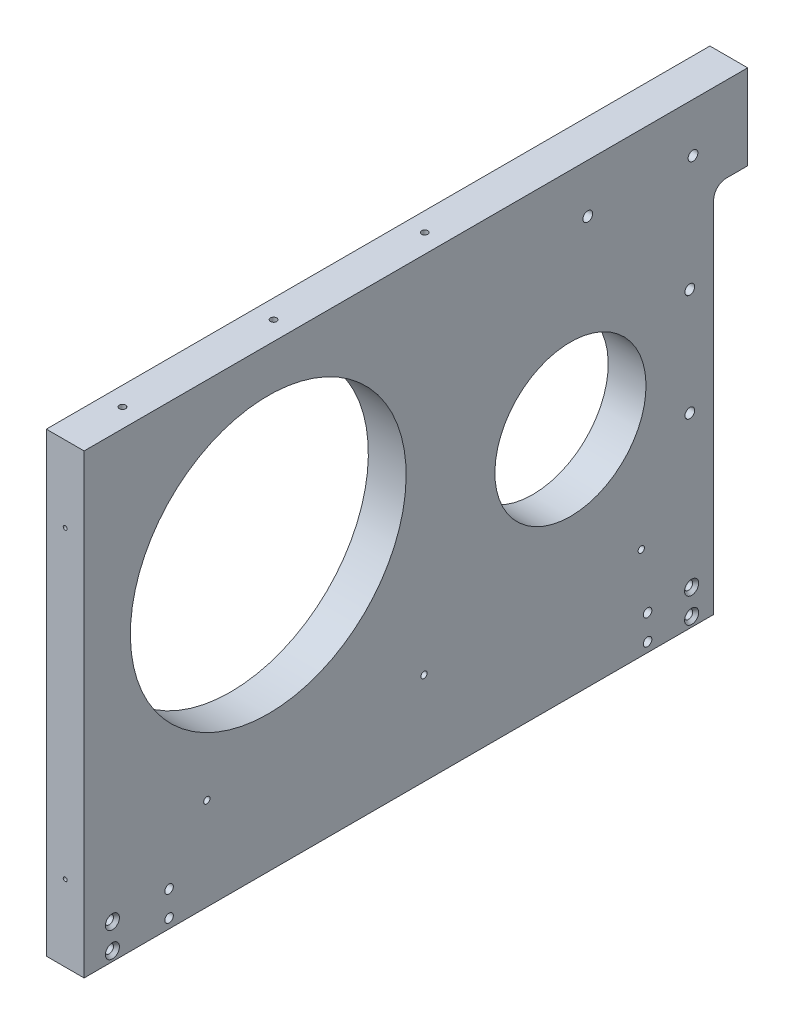
SolidWorks part; units mm, degrees
material "MDF"
ref_plane "Front Plane" through (0, 0, 0) normal (0, 0, 1) x (1, 0, 0)
ref_plane "Top Plane" through (0, 0, 0) normal (0, 1, 0) x (1, 0, 0)
ref_plane "Right Plane" through (0, 0, 0) normal (1, 0, 0) x (0, 0, -1)
sketch "Sketch1" plane through (0, 0, 0) normal (0, 0, 1) x (1, 0, 0)
  line L0 (-296.7037, -233.3625) -> (-271.672, -233.3625) construction
  line L1 (-290.722, -3.175) -> (-271.672, -3.175)
  line L2 (-290.722, -3.175) -> (-290.722, -233.3625)
  line L3 (-290.722, -233.3625) -> (-271.672, -233.3625)
  line L4 (-271.672, -3.175) -> (-271.672, -233.3625)
  dimension "D1" = 19.05
extrude "Boss-Extrude1" add sketch "Sketch1" along normal blind 342.9
sketch "Sketch2" plane through (0, 0, 0) normal (0, 0, 1) x (1, 0, 0)
  line L1 (-199.4987, -156.8808) -> (-434.4987, -156.8808) construction
  line L2 (-271.672, -3.175) -> (-290.722, -3.175) construction
  line L3 (-271.672, -156.8808) -> (-290.722, -156.8808) construction
  line L4 (-271.672, -160.0558) -> (-290.722, -160.0558)
  line L5 (-290.722, -3.175) -> (-271.672, -3.175)
  line L6 (-271.672, -160.0558) -> (-271.672, -3.175)
  line L9 (-290.722, -3.175) -> (-290.722, -160.0558)
  line L10 (-271.672, -233.3625) -> (-271.672, -3.175) construction
  line L11 (-290.722, -3.175) -> (-290.722, -233.3625) construction
  line L12 (-199.4987, -160.0558) -> (-434.4987, -160.0558) construction
  line L13 (-199.4987, -156.8808) -> (-434.4987, -156.8808) construction
  dimension "D1" = 3.175
extrude "Cut-Extrude1" cut sketch "Sketch2" along normal blind 8.255
hole_wizard "15/64 (0.23438) Diameter Hole3" positions "Sketch7" profile "Sketch8" hole size "15/64" standard "ANSI Inch"
sketch "Sketch7" plane through (-182.4037, 1936.854, -6.35) normal (0, 0, -1) x (1, 0, 0)
  point P0 (-262.8265, 2051.0885)
  point P3 (-262.8265, 2014.0687)
  point P6 (-262.8265, 1977.0488)
  point P9 (-98.7933, 2115.9598)
  point P12 (-98.7933, 2151.1665)
sketch "Sketch8" plane through (-445.2302, -114.2346, -6.35) normal (1, 0, 0) x (0, 1, 0)
  line L0 (0, 0) -> (0, 14.4885)
  line L1 (0, 14.4885) -> (2.9766, 12.7)
  line L2 (2.9766, 12.7) -> (2.9766, 0)
  line L3 (2.9766, 0) -> (0, 0)
  line L4 (0, 14.4885) -> (-2.9766, 12.7) construction
  line L5 (0, -6.35) -> (0, 107.95) construction
  dimension "Hole Dia." = 5.9533
  dimension "Hole Depth" = 12.7
  dimension "Drill Angle" = 118
hole_wizard "5/64 (0.07813) Diameter Hole1" positions "Sketch9" profile "Sketch10" hole size "5/64" standard "ANSI Inch"
sketch "Sketch9" plane through (-182.4037, 15.875, 6471.4599) normal (0, 1, 0) x (1, 0, 0)
  line L1 (-1.27, 6109.5099) -> (-1.27, 6338.7449) construction
  point P0 (-262.8265, 6157.4524)
  point P6 (-98.7933, 6157.4524)
  point P18 (-262.8265, 6233.6524)
  point P19 (-98.7933, 6233.6524)
  point P22 (-262.8265, 6309.8524)
  point P23 (-98.7933, 6309.8524)
  point P24 (-267.97, 6119.0349)
  point P34 (-115.57, 6119.0349)
  point P37 (-1.27, 6119.0349)
  point P40 (113.03, 6119.0349)
  point P44 (265.43, 6119.0349)
  point P55 (98.7933, 6309.8524)
  point P56 (262.8265, 6309.8524)
  point P59 (98.7933, 6233.6524)
  point P60 (262.8265, 6233.6524)
  point P63 (98.7933, 6157.4524)
  point P64 (262.8265, 6157.4524)
sketch "Sketch10" plane through (-445.2302, 15.875, 314.0075) normal (1, 0, 0) x (0, 0, 1)
  line L0 (0, 0) -> (0, 39.0539)
  line L1 (0, 39.0539) -> (1.5875, 38.1)
  line L2 (1.5875, 38.1) -> (1.5875, 4.0177)
  line L3 (1.5875, 4.0177) -> (5.08, 0)
  line L4 (5.08, 0) -> (0, 0)
  line L5 (-1.5875, 4.0177) -> (-5.08, 0) construction
  line L6 (0, 39.0539) -> (-1.5875, 38.1) construction
  line L7 (0, -6.35) -> (0, 107.95) construction
  dimension "Hole Dia." = 3.175
  dimension "Hole Depth" = 38.1
  dimension "Near C'Sink Dia." = 10.16
  dimension "Near C'Sink Angle" = 82
  dimension "Drill Angle" = 118
hole_wizard "5/64 (0.07813) Diameter Hole2" positions "Sketch11" profile "Sketch12" hole size "5/64" standard "ANSI Inch"
sketch "Sketch11" plane through (-182.4037, 1936.854, 361.95) normal (0, 0, 1) x (-1, 0, 0)
  line L23 (262.8265, 2088.1084) -> (262.8265, 2038.7486)
  line L24 (262.8265, 2038.7486) -> (262.8265, 1989.3888)
  line L25 (262.8265, 1989.3888) -> (262.8265, 2038.7486)
  line L26 (262.8265, 2038.7486) -> (262.8265, 1989.3888)
  line L27 (262.8265, 1989.3888) -> (262.8265, 1940.029)
  line L33 (98.7933, 2170.2165) -> (98.7933, 2131.8519)
  line L35 (98.7933, 2131.8519) -> (98.7933, 2093.4873)
  line L36 (98.7933, 2093.4873) -> (98.7933, 2055.1227)
  line L37 (98.7933, 2055.1227) -> (98.7933, 2016.7581)
  line L38 (98.7933, 2016.7581) -> (98.7933, 1978.3935)
  line L39 (98.7933, 1978.3935) -> (98.7933, 1940.029)
  line L44 (89.2683, 2123.544) -> (53.561, 2123.544)
  line L46 (53.561, 2123.544) -> (17.8537, 2123.544)
  line L47 (17.8537, 2123.544) -> (-17.8537, 2123.544)
  line L48 (-17.8537, 2123.544) -> (-53.561, 2123.544)
  line L49 (-53.561, 2123.544) -> (-89.2683, 2123.544)
  line L53 (0, 2170.2165) -> (-0.3175, 1940.029) construction
  line L55 (-99.3221, 1978.6668) -> (-99.4279, 1940.3024)
  line L56 (-99.2163, 2017.0312) -> (-99.3221, 1978.6668)
  line L57 (-99.1104, 2055.3957) -> (-99.2163, 2017.0312)
  line L58 (-99.0046, 2093.7601) -> (-99.1104, 2055.3957)
  line L59 (-98.8988, 2132.1245) -> (-99.0046, 2093.7601)
  line L60 (-98.7929, 2170.489) -> (-98.8988, 2132.1245)
  line L61 (-263.3243, 1990.1145) -> (-263.4605, 1940.7549)
  line L62 (-263.1882, 2039.4741) -> (-263.3243, 1990.1145)
  line L63 (-263.3243, 1990.1145) -> (-263.1882, 2039.4741)
  line L64 (-263.1882, 2039.4741) -> (-263.3243, 1990.1145)
  line L65 (-263.052, 2088.8338) -> (-263.1882, 2039.4741)
  point P71 (262.8265, 1964.7089)
  point P79 (262.8265, 2063.4285)
  point P95 (98.7933, 2131.8519)
  point P103 (98.7933, 1978.3935)
  point P126 (53.561, 2123.544)
  point P134 (-53.561, 2123.544)
  point P162 (-98.7933, 1978.3935)
  point P166 (-98.7933, 2131.8519)
  point P167 (-262.8265, 2063.4285)
  point P169 (-262.8265, 1964.7089)
sketch "Sketch12" plane through (80.4228, -27.8549, 361.95) normal (1, 0, 0) x (0, -1, 0)
  line L0 (0, 0) -> (0, 38.6962)
  line L1 (0, 38.6962) -> (0.9923, 38.1)
  line L2 (0.9923, 38.1) -> (0.9923, 4.7024)
  line L3 (0.9923, 4.7024) -> (5.08, 0)
  line L4 (5.08, 0) -> (0, 0)
  line L5 (-0.9923, 4.7024) -> (-5.08, 0) construction
  line L6 (0, 38.6962) -> (-0.9923, 38.1) construction
  line L7 (0, -6.35) -> (0, 107.95) construction
  dimension "Hole Dia." = 1.9845
  dimension "Hole Depth" = 38.1
  dimension "Near C'Sink Dia." = 10.16
  dimension "Near C'Sink Angle" = 82
  dimension "Drill Angle" = 118
hole_wizard "1/8 (0.125) Diameter Hole1" positions "Sketch13" profile "Sketch14" hole size "1/8" standard "ANSI Inch" end condition up to next
sketch "Sketch13" plane through (-290.722, 0, 0) normal (-1, 0, 0) x (0, 0, 1)
  line L4 (317.5, -186.69) -> (280.9875, -186.69)
  line L5 (317.5, -193.04) -> (317.5, -180.34) construction
  line L6 (280.9875, -186.69) -> (244.475, -186.69)
  line L7 (244.475, -186.69) -> (207.9625, -186.69)
  line L8 (207.9625, -186.69) -> (171.45, -186.69)
  line L9 (171.45, -186.69) -> (134.9375, -186.69)
  line L10 (134.9375, -186.69) -> (98.425, -186.69)
  line L11 (98.425, -186.69) -> (61.9125, -186.69)
  line L12 (61.9125, -186.69) -> (25.4, -186.69)
  point P10 (280.9875, -186.69)
  point P18 (171.45, -186.69)
  point P24 (61.9125, -186.69)
sketch "Sketch14" plane through (-290.722, -186.69, 61.9125) normal (0, 1, 0) x (0, 0, 1)
  line L0 (0, 0) -> (0, 19.05)
  line L1 (0, 19.05) -> (1.5875, 19.05)
  line L2 (1.5875, 19.05) -> (1.5875, 3.4925)
  line L3 (1.5875, 3.4925) -> (5.08, 0)
  line L5 (5.08, 0) -> (0, 0)
  line L6 (-1.5875, 3.4925) -> (-5.08, 0) construction
  line L11 (0, -6.35) -> (0, 107.95) construction
  dimension "Thru Hole Dia." = 3.175
  dimension "Thru Hole Depth" = 19.05
  dimension "Near C'Sink Dia." = 10.16
  dimension "Near C'Sink Angle" = 90
hole_wizard "#8 Clearance Hole1" positions "Sketch15" profile "Sketch16" hole size "#8" standard "ANSI Inch" end condition up to next
sketch "Sketch15" plane through (-271.672, 0, 0) normal (1, 0, 0) x (0, 0, -1)
  point P0 (-88.9, -27.7495)
  point P2 (-35.8275, -27.7495)
sketch "Sketch16" plane through (-271.672, -27.7495, 88.9) normal (0, 1, 0) x (0, 0, -1)
  line L0 (0, 0) -> (0, 19.05)
  line L1 (0, 19.05) -> (2.4574, 19.05)
  line L2 (2.4574, 19.05) -> (2.4574, 0)
  line L5 (2.4574, 0) -> (0, 0)
  line L11 (0, -6.35) -> (0, 107.95) construction
  dimension "Thru Hole Dia." = 4.9149
  dimension "Thru Hole Depth" = 19.05
hole_wizard "CSK for #6 Flat Head Machine Screw (100)1" positions "Sketch18" profile "Sketch19" countersink size "#6" standard "ANSI Inch" end condition up to next
sketch "Sketch18" plane through (-271.672, 0, 0) normal (1, 0, 0) x (0, 0, -1)
  point P0 (-36.5125, -215.9)
  point P3 (-36.5125, -228.6)
  point P6 (-328.6125, -215.9)
  point P9 (-328.6125, -228.6)
sketch "Sketch19" plane through (-271.672, -215.9, 36.5125) normal (0, 1, 0) x (0, 0, -1)
  line L0 (0, 0) -> (0, 19.05)
  line L1 (0, 19.05) -> (2.1526, 19.05)
  line L2 (2.1526, 19.05) -> (2.1526, 1.5998)
  line L3 (2.1526, 1.5998) -> (3.5433, 0)
  line L5 (3.5433, 0) -> (0, 0)
  line L6 (-2.1526, 1.5998) -> (-3.5433, 0) construction
  line L11 (0, -6.35) -> (0, 107.95) construction
  dimension "Thru Hole Dia." = 4.3053
  dimension "Thru Hole Depth" = 19.05
  dimension "Near C'Sink Dia." = 7.0866
  dimension "Near C'Sink Angle" = 82
hole_wizard "CSK for #6 Flat Head Machine Screw1" positions "Sketch20" profile "Sketch21" countersink size "#6" standard "ANSI Inch" end condition up to next
sketch "Sketch20" plane through (-290.722, 0, 0) normal (-1, 0, 0) x (0, 0, 1)
  point P0 (58.7375, -228.6)
  point P3 (58.7375, -215.9)
  point P6 (300.0375, -228.6)
  point P9 (300.0375, -215.9)
sketch "Sketch21" plane through (-290.722, -228.6, 58.7375) normal (0, 1, 0) x (0, 0, 1)
  line L0 (0, 0) -> (0, 19.05)
  line L1 (0, 19.05) -> (2.1526, 19.05)
  line L2 (2.1526, 19.05) -> (2.1526, 1.5998)
  line L3 (2.1526, 1.5998) -> (3.5433, 0)
  line L5 (3.5433, 0) -> (0, 0)
  line L6 (-2.1526, 1.5998) -> (-3.5433, 0) construction
  line L11 (0, -6.35) -> (0, 107.95) construction
  dimension "Thru Hole Dia." = 4.3053
  dimension "Thru Hole Depth" = 19.05
  dimension "Near C'Sink Dia." = 7.0866
  dimension "Near C'Sink Angle" = 82
sketch "Sketch22" plane through (-290.722, 0, 0) normal (-1, 0, 0) x (0, 0, 1)
  line L1 (0, -233.3625) -> (25.4, -233.3625)
  line L2 (0, -233.3625) -> (0, -45.974)
  line L3 (0, -45.974) -> (25.4, -45.974)
  line L4 (25.4, -233.3625) -> (25.4, -45.974)
  line L5 (11.33, -45.974) -> (60.325, -45.974) construction
  dimension "D1" = 25.4
extrude "Cut-Extrude3" cut sketch "Sketch22" against normal up to next
fillet "Fillet1" radius 6.35 1 edges at (-281.197, -45.974, 25.4)
hole_wizard "#8 Clearance Hole2" positions "Sketch23" profile "Sketch24" hole size "#8" standard "ANSI Inch" end condition through all
sketch "Sketch23" plane through (-271.672, 0, 0) normal (1, 0, 0) x (0, 0, -1)
  point P0 (-37.4475, -139.372)
  point P3 (-37.4475, -85.397)
sketch "Sketch24" plane through (-271.672, -139.372, 37.4475) normal (0, 1, 0) x (0, 0, -1)
  line L0 (0, 0) -> (0, 19.05)
  line L1 (0, 19.05) -> (2.4574, 19.05)
  line L2 (2.4574, 19.05) -> (2.4574, 0)
  line L5 (2.4574, 0) -> (0, 0)
  line L11 (0, -6.35) -> (0, 107.95) construction
  dimension "Thru Hole Dia." = 4.9149
  dimension "Thru Hole Depth" = 19.05
sketch "Sketch17" plane through (-290.722, 0, 0) normal (-1, 0, 0) x (0, 0, 1)
  line L0 (250.0313, -186.69) -> (250.0313, -3.175) construction
  line L2 (342.9, -3.175) -> (8.255, -3.175) construction
  line L4 (280.9875, -186.69) -> (171.45, -186.69) construction
  line L5 (97.6313, -186.69) -> (97.6313, -45.974) construction
  line L6 (60.325, -45.974) -> (117.475, -45.974) construction
  circle A0 centre (250.0313, -94.9325) radius 69.5325
  circle A1 centre (97.6313, -116.332) radius 38.1
  point P17 (250.0313, -94.9325)
  point P18 (250.0313, -164.465)
  point P19 (97.6313, -94.9325)
  point P26 (97.6313, -173.99)
  dimension "D4" = 76.2
  dimension "D1" = 22.225
  dimension "D2" = 12.7
  dimension "D3" = 152.4
extrude "Cut-Extrude2" cut sketch "Sketch17" against normal up to next
